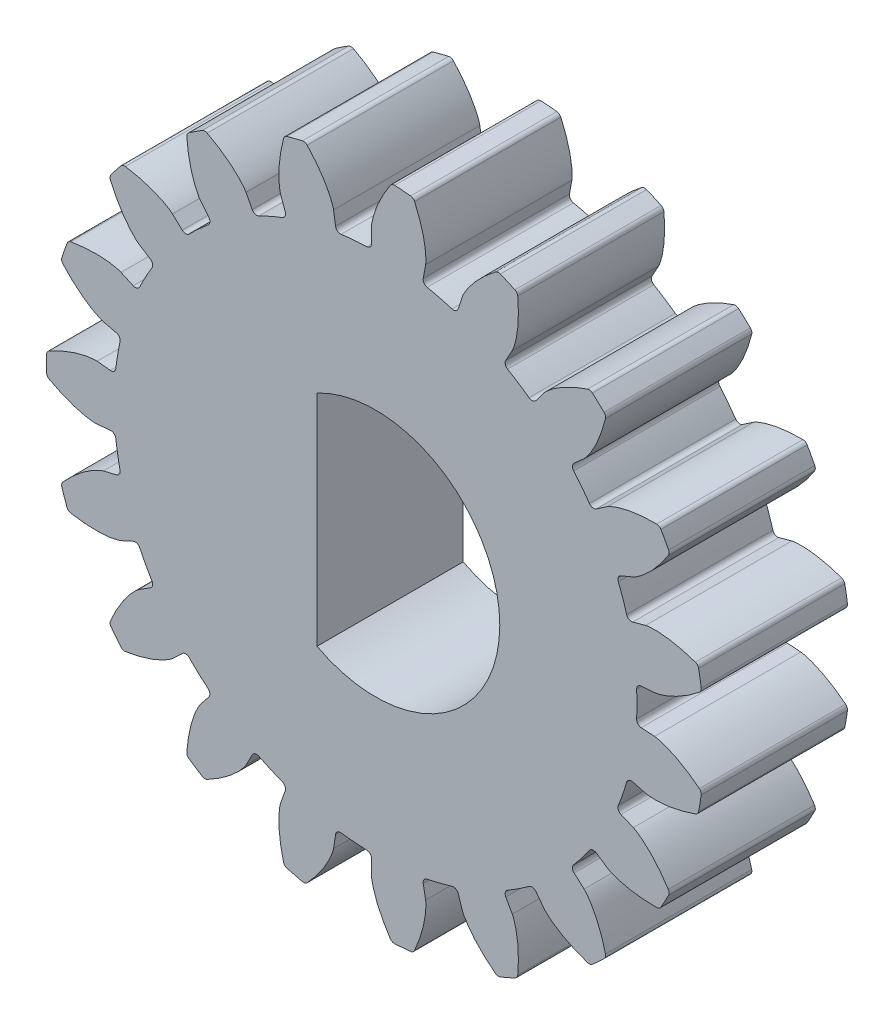
SolidWorks part; units mm, degrees
ref_plane "Front Plane" through (0, 0, 0) normal (0, 0, 1) x (1, 0, 0)
ref_plane "Top Plane" through (0, 0, 0) normal (0, 1, 0) x (1, 0, 0)
ref_plane "Right Plane" through (0, 0, 0) normal (1, 0, 0) x (0, 0, -1)
sketch "Sketch10" plane through (0, 0, 0) normal (0, 0, 1) x (1, 0, 0)
  circle A0 centre (0, 0) radius 22.5
  circle A1 centre (0, 0) radius 1.25
  dimension "D1" = 2.5
  dimension "D2" = 45
extrude "Boss-Extrude5" add sketch "Sketch10" along normal blind 10
sketch "Sketch11" plane through (0, 0, 10) normal (0, 0, 1) x (1, 0, 0)
  line L0 (0, 0) -> (17.88, 0) construction
  line L3 (17.88, 0) -> (22.5005, 0)
  line L4 (0, 0) -> (17.839, 1.2108) construction
  line L5 (19.0859, 1.2954) -> (17.839, 1.2108)
  circle A0 centre (0, 0) radius 17.88 construction
  circle A1 centre (0, 0) radius 19.13 construction
  circle A2 centre (0, 0) radius 20.36 construction
  circle A11 centre (0, 0) radius 22.5005 construction
  arc A12 (22.5005, 0) -> (22.3031, 2.9739) centre (0, 0) ccw
  arc A13 (17.88, 0) -> (17.839, 1.2108) centre (0, 0) ccw
  spline S0 degree 4 poles (19.0859, 1.2954) (19.0913, 1.2959) (19.1065, 1.2973) (19.135, 1.3009) (19.1815, 1.308) (19.2405, 1.3189) (19.3165, 1.335) (19.4057, 1.3566) (19.5032, 1.3831) (19.6089, 1.415) (19.7138, 1.4494) (19.8179, 1.4861) (19.9212, 1.5249) (20.0458, 1.5745) (20.1943, 1.6376) (20.3667, 1.7165) (20.5606, 1.8121) (20.7565, 1.9161) (20.9477, 2.0237) (21.139, 2.1386) (21.3228, 2.254) (21.5117, 2.38) (21.685, 2.4995) (21.8768, 2.6401) (22.0309, 2.7556) (22.2316, 2.915) (22.3493, 3.0113) (22.4861, 3.1265) (22.5464, 3.1789) (22.5835, 3.2111) knots 0 0 0 0 0 0.005377 0.015084 0.028532 0.04661 0.064855 0.092111 0.119476 0.146842 0.174209 0.201575 0.228941 0.256307 0.307035 0.361767 0.4165 0.471232 0.525964 0.580697 0.635429 0.690161 0.744894 0.799626 0.854358 0.909091 0.954545 1 1 1 1 1 construction
  spline S1 degree 4 poles (19.0859, 1.2954) (19.0913, 1.2959) (19.1065, 1.2973) (19.135, 1.3009) (19.1815, 1.308) (19.2405, 1.3189) (19.3165, 1.335) (19.4057, 1.3566) (19.5032, 1.3831) (19.6089, 1.415) (19.7138, 1.4494) (19.8179, 1.4861) (19.9212, 1.5249) (20.0458, 1.5745) (20.1943, 1.6376) (20.3667, 1.7165) (20.5606, 1.8121) (20.7565, 1.9161) (20.9477, 2.0237) (21.139, 2.1386) (21.3228, 2.254) (21.5117, 2.38) (21.685, 2.4995) (21.8768, 2.6401) (22.0309, 2.7556) (22.1881, 2.8805) (22.2643, 2.9421) (22.3031, 2.9739) knots 0 0 0 0 0 0.005377 0.015084 0.028532 0.04661 0.064855 0.092111 0.119476 0.146842 0.174209 0.201575 0.228941 0.256307 0.307035 0.361767 0.4165 0.471232 0.525964 0.580697 0.635429 0.690161 0.744894 0.799626 0.854358 0.909091 0.909091 0.909091 0.909091 0.909091
  dimension "D1" = 40.72
  dimension "D2" = 38.26
  dimension "D3" = 35.76
extrude "Cut-Extrude1" cut sketch "Sketch11" against normal through all
mirror "Mirror1" about plane through (17.88, 0, 0) normal (0, -1, 0) of "Cut-Extrude1"
fillet "Fillet1" radius 0.34 4 edges at (17.839, -1.2108, 5) (22.3026, -2.9735, 5) (22.3026, 2.9735, 5) (17.839, 1.2108, 5)
pattern_circular "CirPattern1" count 19 over 360 about axis through (0, 0, 10) along (0, 0, -1) of "Cut-Extrude1", "Mirror1", "Fillet1" reverse direction yes
sketch "Sketch12" plane through (0, 0, 10) normal (0, 0, 1) x (1, 0, 0)
  line L0 (-2.8, 0) -> (-4, 0) construction
  line L1 (-4, 0) -> (-4, 7.5)
  line L2 (-4, 0) -> (-4, -7.5)
  arc A0 (-4, -7.5) -> (-4, 7.5) centre (0, 0) ccw
  circle A1 centre (0, 0) radius 2.8 construction
  point P6 (0, 0)
  dimension "D1" = 17
  dimension "D2" = 5.6
  dimension "D3" = 1.2
extrude "Cut-Extrude2" cut sketch "Sketch12" against normal through all
equation "\"P\"= 0.466657"
equation "\"z\" = 19"
equation "\"α\"= 20"
equation "\"s\"= 5"
equation "\"D_b\"= 2.5"
equation "\"c\"= 0.157 / \"P\""
equation "\"D_p\"= \"z\" / \"P\""
equation "\"D_base\"= \"D_p\" * cos ( \"α\" )"
equation "\"h_a\"= 1 / \"P\""
equation "\"h_d\"= 1 / \"P\" + \"c\""
equation "\"P_c\"= pi / \"P\""
equation "\"D_a\"= \"D_p\" + ( 2 * \"h_a\" )"
equation "\"D_d\"= \"D_p\" - ( 2 * \"h_d\" )"
equation "\"φ\"= 360 / \"z\""
equation "\"α_inv\"= ( ( \"D_p\" ^ 2 - \"D_base\" ^ 2 ) ^ 0.5 / \"D_base\" ) * 180 / pi - \"α\""
equation "\"β_inv\"= ( \"φ\" / 4 ) - \"α_inv\""
equation "\"ζ\"= ( ( \"D_a\" / 2 ) ^ 2 - ( \"D_base\" / 2 ) ^ 2 ) ^ 0.5 * 2 / \"D_base\""
